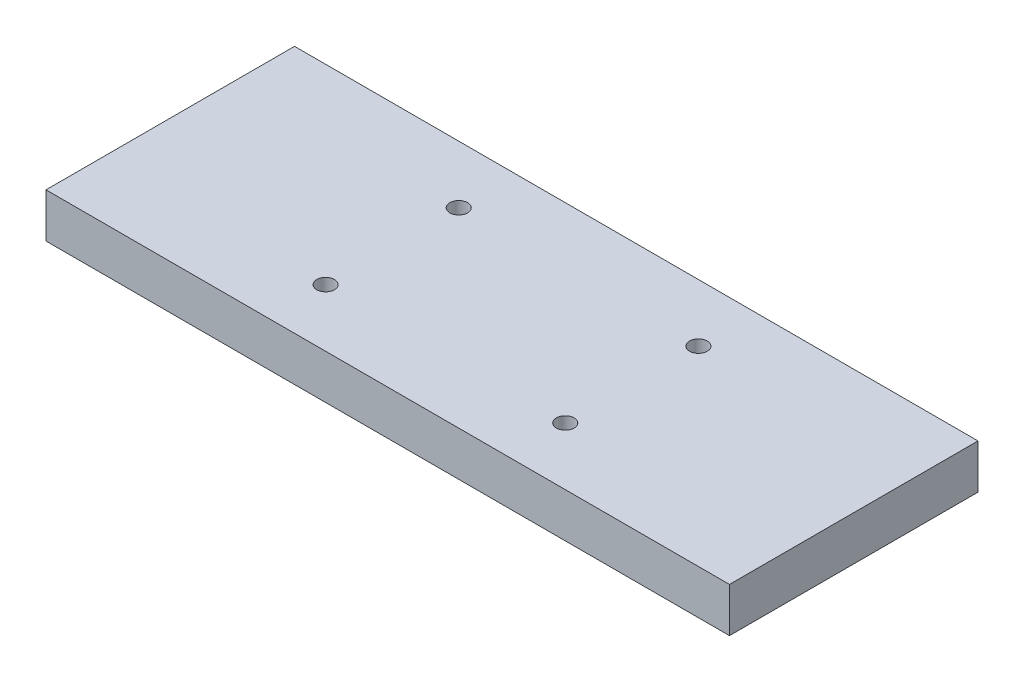
SolidWorks part; units mm, degrees
ref_plane "Front Plane" through (0, 0, 0) normal (0, 0, 1) x (1, 0, 0)
ref_plane "Top Plane" through (0, 0, 0) normal (0, 1, 0) x (1, 0, 0)
ref_plane "Right Plane" through (0, 0, 0) normal (1, 0, 0) x (0, 0, -1)
sketch "Sketch1" plane through (0, 0, 0) normal (0, 1, 0) x (1, 0, 0)
  line L1 (77, 28) -> (-77, 28)
  line L2 (77, 28) -> (77, -28)
  line L3 (77, -28) -> (-77, -28)
  line L4 (-77, 28) -> (-77, -28)
  line L5 (77, 28) -> (-77, -28) construction
  line L6 (77, -28) -> (-77, 28) construction
  point P0 (0, 0)
  dimension "D1" = 154
  dimension "D2" = 56
extrude "Boss-Extrude1" add sketch "Sketch1" along normal blind 10
sketch "Sketch4" plane through (0, 10, 0) normal (0, 1, 0) x (1, 0, 0)
  line L0 (77, 0) -> (-77, 0) construction
  line L1 (0, 28) -> (0, -28) construction
  line L2 (-77, 28) -> (-77, -28) construction
  line L3 (-77, -28) -> (77, -28) construction
  circle A0 centre (-27, 15) radius 2
  circle A1 centre (27, 15) radius 2
  circle A2 centre (27, -15) radius 2
  circle A3 centre (-27, -15) radius 2
  point P2 (-77, 0)
  point P6 (0, 0)
  point P10 (0, 0)
  point P13 (0, -28)
  dimension "D1" = 4
  dimension "D2" = 27
  dimension "D3" = 15
hole_wizard "Ø4.0mm Dowel Hole2" positions "3DSketch2" profile "Sketch5" hole size "Ø4.0" standard "ANSI Metric"
sketch3d "3DSketch2"
  point P0 (-27, 10, -15)
  point P3 (-27, 10, 15)
  point P6 (27, 10, 15)
  point P9 (27, 10, -15)
sketch "Sketch5" plane through (-27, 10, -15) normal (1, 0, 0) x (0, 0, 1)
  line L0 (0, 0) -> (0, 7.2017)
  line L1 (0, 7.2017) -> (2, 6)
  line L2 (2, 6) -> (2, 0)
  line L5 (2, 0) -> (0, 0)
  line L10 (0, 7.2017) -> (-2, 6) construction
  line L11 (0, -6.35) -> (0, 107.95) construction
  dimension "Hole Dia." = 4
  dimension "Hole Depth" = 6
  dimension "Drill Angle" = 118
